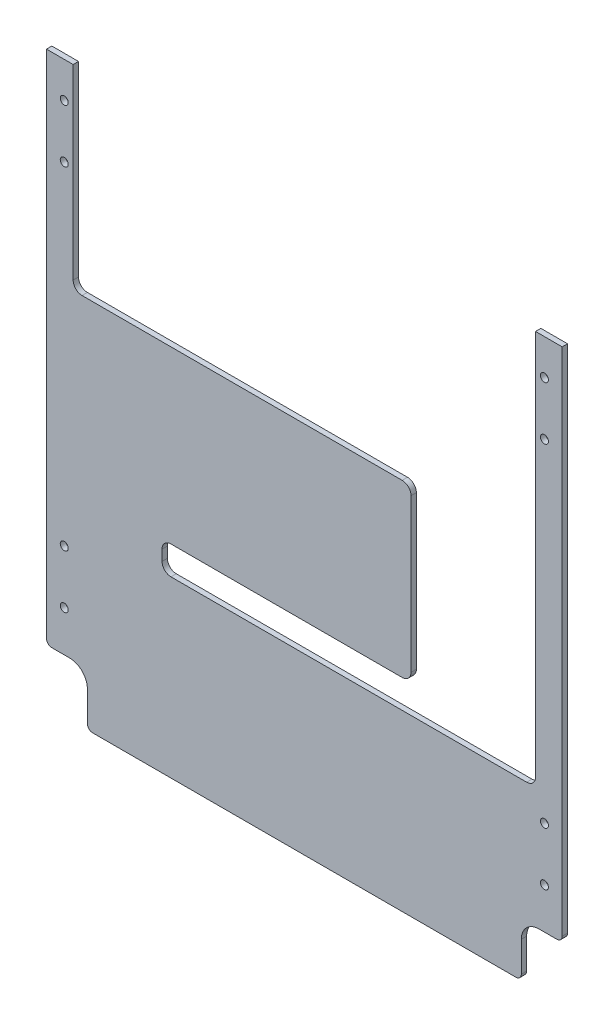
SolidWorks part; units mm, degrees
ref_plane "Front" through (0, 0, 0) normal (0, 0, 1) x (1, 0, 0)
ref_plane "Top" through (0, 0, 0) normal (0, 1, 0) x (1, 0, 0)
ref_plane "Right" through (0, 0, 0) normal (1, 0, 0) x (0, 0, -1)
sketch "Esquisse1" plane through (0, 0, 0) normal (0, 0, 1) x (1, 0, 0)
  line L1 (0, 0) -> (290, 0)
  line L2 (0, 0) -> (0, 320)
  line L3 (0, 320) -> (290, 320)
  line L4 (290, 0) -> (290, 320)
  dimension "D1" = 290
  dimension "D2" = 320
extrude "Boss.-Extru.1" add sketch "Esquisse1" along normal blind 3
sketch "Esquisse2" plane through (0, 0, 3) normal (0, 0, 1) x (1, 0, 0)
  line L0 (145, 0) -> (145, 56.1801) construction
  line L1 (290, 0) -> (267, 0)
  line L2 (290, 0) -> (290, 30)
  line L3 (290, 30) -> (267, 30)
  line L4 (267, 0) -> (267, 30)
  line L5 (0, 0) -> (290, 0) construction
  line L6 (23, 0) -> (23, 30)
  line L7 (0, 30) -> (23, 30)
  line L8 (0, 0) -> (0, 30)
  line L9 (0, 0) -> (23, 0)
  dimension "D1" = 23
  dimension "D2" = 30
extrude "Enlèv. mat.-Extru.1" cut sketch "Esquisse2" against normal through all both and the other way through all
fillet "Congé1" radius 10 2 edges at (267, 30, 1.5) (23, 30, 1.5)
fillet "Congé2" radius 3 4 edges at (290, 30, 1.5) (0, 30, 1.5) (23, 0, 1.5) (267, 0, 1.5)
sketch "Esquisse3" plane through (0, 0, 3) normal (0, 0, 1) x (1, 0, 0)
  line L0 (290, 320) -> (0, 320) construction
  line L1 (85, 320) -> (205, 320)
  line L2 (85, 320) -> (85, 210)
  line L3 (85, 210) -> (205, 210)
  line L4 (205, 320) -> (205, 210)
  line L5 (145, 210) -> (145, 0) construction
  line L6 (26, 0) -> (264, 0) construction
  dimension "D1" = 120
  dimension "D2" = 110
extrude "Enlèv. mat.-Extru.2" cut sketch "Esquisse3" against normal through all both and the other way through all
sketch "Esquisse4" plane through (0, 0, 3) normal (0, 0, 1) x (1, 0, 0)
  line L0 (290, 320) -> (205, 320) construction
  line L1 (205, 320) -> (275, 320)
  line L2 (205, 320) -> (205, 98)
  line L3 (205, 98) -> (275, 98)
  line L4 (275, 320) -> (275, 98)
  line L5 (290, 33) -> (290, 320) construction
  line L6 (205, 320) -> (205, 210) construction
  line L7 (26, 0) -> (264, 0) construction
  dimension "D1" = 15
  dimension "D2" = 98
extrude "Enlèv. mat.-Extru.3" cut sketch "Esquisse4" against normal through all both and the other way through all
sketch "Esquisse5" plane through (0, 0, 3) normal (0, 0, 1) x (1, 0, 0)
  line L0 (85, 320) -> (0, 320) construction
  line L1 (85, 210) -> (15, 210)
  line L2 (85, 210) -> (85, 320)
  line L3 (85, 320) -> (15, 320)
  line L4 (15, 210) -> (15, 320)
  line L5 (0, 320) -> (0, 33) construction
  dimension "D1" = 15
extrude "Enlèv. mat.-Extru.4" cut sketch "Esquisse5" against normal through all both and the other way through all
sketch "Esquisse6" plane through (0, 0, 3) normal (0, 0, 1) x (1, 0, 0)
  line L0 (205, 98) -> (205, 210) construction
  line L1 (205, 98) -> (65, 98)
  line L2 (205, 98) -> (205, 114)
  line L3 (205, 114) -> (65, 114)
  line L4 (65, 98) -> (65, 114)
  line L5 (26, 0) -> (264, 0) construction
  line L6 (0, 320) -> (0, 33) construction
  dimension "D1" = 16
  dimension "D2" = 98
  dimension "D3" = 65
extrude "Enlèv. mat.-Extru.5" cut sketch "Esquisse6" against normal through all both and the other way through all
fillet "Congé3" radius 5 6 edges at (275, 98, 1.5) (65, 98, 1.5) (65, 114, 1.5) (205, 114, 1.5) (205, 210, 1.5) (15, 210, 1.5)
sketch "Esquisse7" plane through (0, 0, 3) normal (0, 0, 1) x (1, 0, 0)
  line L0 (280, 320) -> (280, 300) construction
  line L1 (290, 320) -> (275, 320) construction
  line L2 (275, 320) -> (275, 103) construction
  line L3 (280, 300) -> (280, 270) construction
  line L4 (145, 0) -> (145, 300) construction
  line L5 (26, 0) -> (264, 0) construction
  line L6 (10, 300) -> (10, 270) construction
  line L7 (10, 320) -> (10, 300) construction
  line L8 (0, 176.5) -> (290, 176.5) construction
  line L9 (0, 320) -> (0, 33) construction
  line L10 (290, 33) -> (290, 320) construction
  line L11 (280, 53) -> (280, 83) construction
  line L12 (280, 33) -> (280, 53) construction
  line L13 (10, 33) -> (10, 53) construction
  line L14 (10, 53) -> (10, 83) construction
  circle A0 centre (280, 300) radius 2.25
  circle A1 centre (280, 270) radius 2.25
  circle A2 centre (10, 270) radius 2.25
  circle A3 centre (10, 300) radius 2.25
  circle A4 centre (280, 83) radius 2.25
  circle A5 centre (280, 53) radius 2.25
  circle A6 centre (10, 53) radius 2.25
  circle A7 centre (10, 83) radius 2.25
  dimension "D2" = 4.5
  dimension "D4" = 30
  dimension "D1" = 5
  dimension "D3" = 20
extrude "Enlèv. mat.-Extru.6" cut sketch "Esquisse7" against normal through all both and the other way through all
